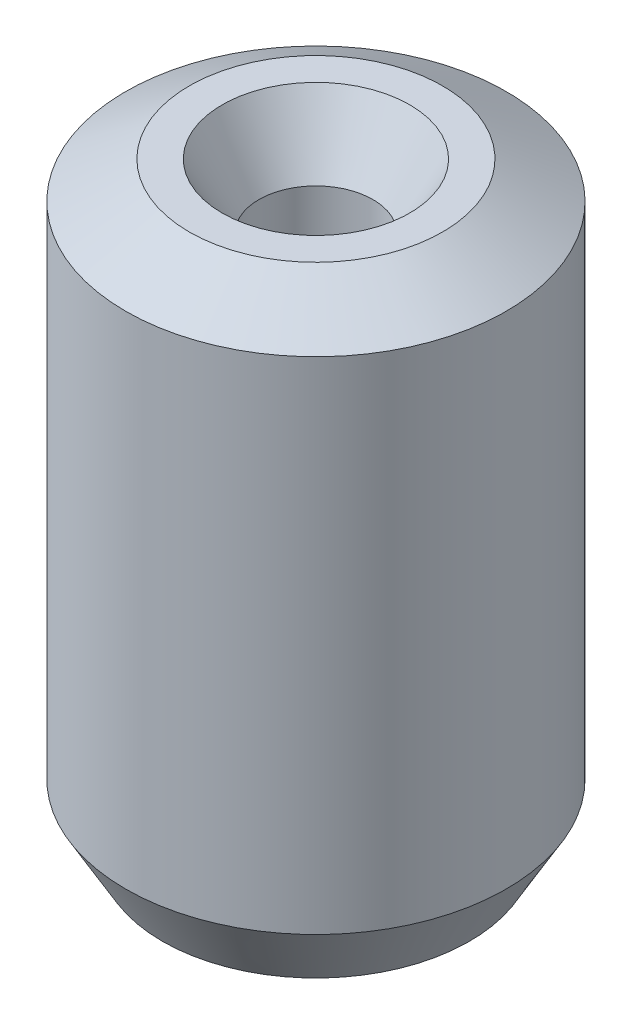
SolidWorks part; units mm, degrees
ref_plane "Front Plane" through (0, 0, 0) normal (0, 0, 1) x (1, 0, 0)
ref_plane "Top Plane" through (0, 0, 0) normal (0, 1, 0) x (1, 0, 0)
ref_plane "Right Plane" through (0, 0, 0) normal (1, 0, 0) x (0, 0, -1)
sketch "Sketch1" plane through (0, 0, 0) normal (0, 1, 0) x (1, 0, 0)
  circle A0 centre (0, 0) radius 5
  dimension "SLEEVE_OD" = 10
extrude "Boss-Extrude1" add sketch "Sketch1" along normal blind 15.7862
sketch "Sketch2" plane through (0, 0, 0) normal (0, 1, 0) x (1, 0, 0)
  circle A0 centre (0, 0) radius 1.4985
  dimension "BORE_D" = 2.9971
extrude "Cut-Extrude1" cut sketch "Sketch2" along normal through all
chamfer "Chamfer1" distance 0.9659 angle 60 4 edges at (0, 15.7862, 1.4985) (0, 0, 1.4985) (0, 0, 5) (0, 15.7862, 5) first distance on face at (0, 15.7862, 1.4985) first distance on face at (0, 0, 1.4985) first distance on face at (0, 15.7862, 5)
